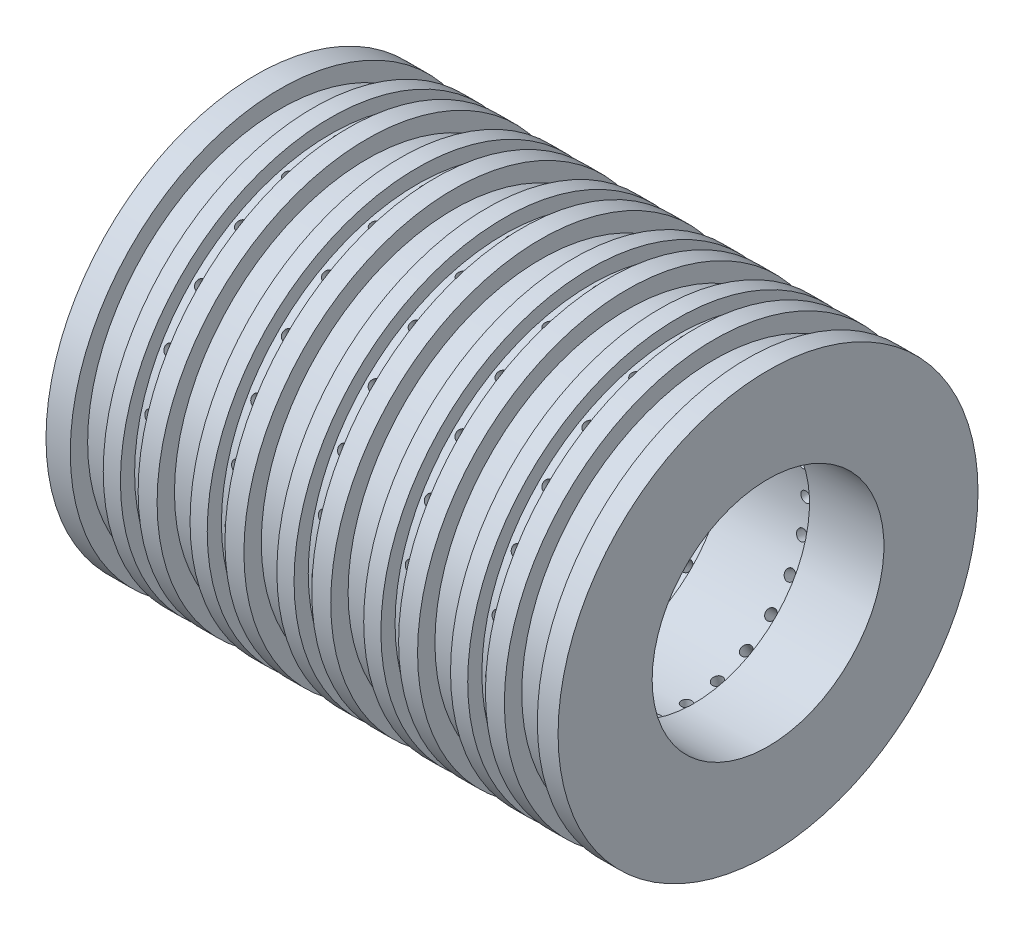
SolidWorks part; units mm, degrees
note: '?' marks a value the reader was unsure of.
ref_plane "Front Plane" through (0, 0, 0) normal (0, 0, 1) x (1, 0, 0)
ref_plane "Top Plane" through (0, 0, 0) normal (0, 1, 0) x (1, 0, 0)
ref_plane "Right Plane" through (0, 0, 0) normal (1, 0, 0) x (0, 0, -1)
sketch "Sketch1" plane through (0, 0, 0) normal (0, 0, 1) x (1, 0, 0)
  line L0 (0, 0) -> (36.5459, 0) construction
  line L1 (-6.477, 9.5758) -> (-6.477, 15.0495)
  line L3 (30.226, 15.0495) -> (30.226, 8.3058)
  line L4 (30.226, 8.3058) -> (24.892, 8.3058)
  line L5 (24.892, 8.3058) -> (24.892, 8.5598)
  line L6 (24.892, 8.5598) -> (18.669, 8.5598)
  line L7 (18.669, 8.5598) -> (18.669, 8.8138)
  line L8 (18.669, 8.8138) -> (12.446, 8.8138)
  line L9 (12.446, 8.8138) -> (12.446, 9.0678)
  line L10 (12.446, 9.0678) -> (6.223, 9.0678)
  line L11 (6.223, 9.0678) -> (6.223, 9.3218)
  line L12 (6.223, 9.3218) -> (0, 9.3218)
  line L13 (0, 9.3218) -> (0, 9.5758)
  line L14 (0, 9.5758) -> (-6.477, 9.5758)
  line L15 (-6.477, 15.0495) -> (-3.937, 15.0495)
  line L16 (-1.143, 15.0495) -> (-1.143, 14.0335)
  line L17 (-1.143, 14.0335) -> (0.127, 14.0335)
  line L18 (0.127, 14.0335) -> (0.127, 15.0495)
  line L19 (0.127, 15.0495) -> (2.4765, 15.0495)
  line L20 (5.08, 15.0495) -> (5.08, 14.0335)
  line L21 (5.08, 14.0335) -> (6.35, 14.0335)
  line L22 (6.35, 14.0335) -> (6.35, 15.0495)
  line L23 (6.35, 15.0495) -> (8.6995, 15.0495)
  line L24 (11.303, 15.0495) -> (11.303, 14.0335)
  line L25 (11.303, 14.0335) -> (12.573, 14.0335)
  line L26 (12.573, 14.0335) -> (12.573, 15.0495)
  line L27 (12.573, 15.0495) -> (14.9225, 15.0495)
  line L28 (17.526, 15.0495) -> (17.526, 14.0335)
  line L29 (17.526, 14.0335) -> (18.796, 14.0335)
  line L30 (18.796, 14.0335) -> (18.796, 15.0495)
  line L31 (18.796, 15.0495) -> (21.1455, 15.0495)
  line L32 (23.749, 15.0495) -> (23.749, 14.0335)
  line L33 (23.749, 14.0335) -> (25.019, 14.0335)
  line L34 (25.019, 14.0335) -> (25.019, 15.0495)
  line L35 (25.019, 15.0495) -> (27.4955, 15.0495)
  line L36 (-3.683, 15.0495) -> (-1.143, 15.0495)
  line L37 (2.7305, 15.0495) -> (5.08, 15.0495)
  line L38 (8.9535, 15.0495) -> (11.303, 15.0495)
  line L39 (15.1765, 15.0495) -> (17.526, 15.0495)
  line L40 (21.3995, 15.0495) -> (23.749, 15.0495)
  line L41 (27.7495, 15.0495) -> (30.226, 15.0495)
  line L42 (-3.937, 15.0495) -> (-3.683, 15.0495) construction
  line L43 (2.4765, 15.0495) -> (2.7305, 15.0495) construction
  line L44 (8.6995, 15.0495) -> (8.9535, 15.0495) construction
  line L45 (14.9225, 15.0495) -> (15.1765, 15.0495) construction
  line L46 (21.1455, 15.0495) -> (21.3995, 15.0495) construction
  line L47 (27.4955, 15.0495) -> (27.7495, 15.0495) construction
  arc A9 (21.3995, 15.0495) -> (21.1455, 15.0495) centre (21.2725, 15.0495) ccw
  arc A10 (15.1765, 15.0495) -> (14.9225, 15.0495) centre (15.0495, 15.0495) ccw
  arc A11 (8.9535, 15.0495) -> (8.6995, 15.0495) centre (8.8265, 15.0495) ccw
  arc A12 (2.7305, 15.0495) -> (2.4765, 15.0495) centre (2.6035, 15.0495) ccw
  arc A13 (-3.683, 15.0495) -> (-3.937, 15.0495) centre (-3.81, 15.0495) ccw
  arc A14 (27.7495, 15.0495) -> (27.4955, 15.0495) centre (27.6225, 15.0495) ccw
  point P37 (-6.477, 12.3126)
  dimension "D13" = 0.254
  dimension "D2" = 0.254
  dimension "D4" = 15.0495
  dimension "D5" = 1.27
  dimension "D6" = 1.016
  dimension "D8" = 1.27
  dimension "D9" = 1.016
  dimension "D10" = 1.016
  dimension "D11" = 1.27
  dimension "D3" = 6.223
  dimension "D12" = 36.703
  dimension "D14" = 9.5758
  dimension "D7" = 0.127
  dimension "D15" = 0.127
  dimension "D16" = 0.127
  dimension "D17" = 0.127
  dimension "D18" = 0.127
  dimension "D19" = 5.334
  dimension "D20" = 6.477
revolve "Revolve1" add sketch "Sketch1" angle 360 about L0
ref_plane "Plane1" through (-0.508, 0, 0) normal (-1, 0, 0) x (0, 0, 1)
ref_plane "Plane2" through (5.715, 0, 0) normal (-1, 0, 0) x (0, 0, 1)
ref_plane "Plane3" through (11.938, 0, 0) normal (1, 0, 0) x (0, 0, -1)
ref_plane "Plane4" through (18.161, 0, 0) normal (-1, 0, 0) x (0, 0, 1)
ref_plane "Plane5" through (24.384, 0, 0) normal (1, 0, 0) x (0, 0, -1)
ref_plane "Plane6" through (0, 15.0495, 0) normal (0, 1, 0) x (1, 0, 0)
ref_axis "Axis1" through (0, 0, 0) along (-1, 0, 0)?
sketch "Sketch4" plane through (-0.508, 0, 0) normal (-1, 0, 0) x (0, 0, 1)
  point P0 (0, 0)
sketch "Sketch5" plane through (5.715, 0, 0) normal (-1, 0, 0) x (0, 0, 1)
  point P0 (0, 0)
sketch "Sketch6" plane through (11.938, 0, 0) normal (1, 0, 0) x (0, 0, -1)
  point P0 (0, 0)
sketch "Sketch7" plane through (18.161, 0, 0) normal (-1, 0, 0) x (0, 0, 1)
  point P0 (0, 0)
sketch "Sketch8" plane through (24.384, 0, 0) normal (1, 0, 0) x (0, 0, -1)
  point P0 (0, 0)
sketch "Sketch9" plane through (0, 15.0495, 0) normal (0, 1, 0) x (1, 0, 0)
  point P0 (24.384, 0)
  point P2 (18.161, 0)
  point P4 (11.938, 0)
  point P6 (5.715, 0)
  point P11 (-0.508, 0)
hole_wizard "#69 (0.0292) Diameter Hole1" positions "Sketch9" profile "Sketch10" hole size "#69" standard "ANSI Inch" end condition up to next
sketch "Sketch10" plane through (24.384, 15.0495, 0) normal (1, 0, 0) x (0, 0, 1)
  line L0 (0, 0) -> (0, 6.4897)
  line L1 (0, 6.4897) -> (0.3708, 6.4897)
  line L2 (0.3708, 6.4897) -> (0.3708, 0)
  line L5 (0.3708, 0) -> (0, 0)
  line L11 (0, -6.35) -> (0, 107.95) construction
  dimension "Thru Hole Dia." = 0.7417
  dimension "Thru Hole Depth" = 6.4897
pattern_circular "CirPattern1" count 24 every 15 about axis through (0, 0, 0) along (-1, 0, 0) of "#69 (0.0292) Diameter Hole1"
sketch "Sketch11" plane through (30.226, 0, 0) normal (1, 0, 0) x (0, 0, -1)
  circle A0 centre (0, 0) radius 13.8049
  circle A1 centre (0, 0) radius 17.8435
  dimension "D1" = 27.6098
  dimension "D2" = 35.687
extrude "Cut-Extrude1" cut sketch "Sketch11" against normal blind 2.3622 from offset 1.4859 offset against normal yes
pattern_linear "LPattern1" count 6 spacing 6.223 along (-1, 0, 0) of "Cut-Extrude1"
equation "\"kero_radius\"=0.23622in"
equation "\"lox_radius\"=0.23622in"
equation "\"Cavity_width\"=0.031in"
equation "\"tooth_width\"=0.01in"
equation "\"cavity_depth\"=0.031in"
equation "\"seal_step\"=0.01in"
equation "\"purge_length\"=0.04in"
equation "\"D2@Sketch1\"=\"seal_step\""
equation "\"insert_radius\" = 0.5925in"
equation "\"recycle_groove width\" = 0.05in"
equation "\"D5@Sketch1\"=\"recycle_groove width\""
equation "\"recycle_groove_depth\" = 0.04in"
equation "\"D6@Sketch1\"=\"recycle_groove_depth\""
equation "\"N2_purge_width\"= .05in"
equation "\"N2_purge_depth\"= .04in"
equation "\"drain_width\"= .05in"
equation "\"drain_depth\"= .04in"
equation "\"D9@Sketch1\"=\"drain_depth\""
equation "\"D8@Sketch1\"=\"drain_width\""
equation "\"D10@Sketch1\"=\"N2_purge_depth\""
equation "\"D11@Sketch1\"=\"N2_purge_width\""
equation "\"radial_clearance\"= .002in"
equation "\"D3@Sketch1\"=\"tooth_width\"*5+\"Cavity_width\"*5+\"purge_length\""
equation "\"Insert_Length\"= \"D12@Sketch1\""
equation "\"InsertLength\"= 1.445in"
equation "\"D4@Sketch1\"=\"insert_radius\""
equation "\"bumb_radius\"= 0.01"
equation "\"D13@Sketch1\"=\"bumb_radius\""
equation "\"bearing_radius\"= 0.629921"
equation "\"bearing_width\"=0.393701"
equation "\"IPS_flange_width\"= .25in"
equation "\"IPS_flange_radius\" = 2.2in"
equation "\"IPS_LOX_male_radius\"= .9in"
equation "\"IPS_Kero_male_radius\" = .9in"
equation "\"IPS_radius\"= 1.4in"
equation "\"lox_in_radius\"=.375in"
equation "\"D14@Sketch1\"=\"lox_in_radius\"+\"radial_clearance\""
equation "\"D7@Sketch1\"=(\"drain_width\"-\"purge_length\")/2"
equation "\"D15@Sketch1\"=(\"drain_width\"-\"purge_length\")/2"
equation "\"D16@Sketch1\"=(\"drain_width\"-\"purge_length\")/2"
equation "\"D17@Sketch1\"=(\"drain_width\"-\"purge_length\")/2"
equation "\"D18@Sketch1\"=(\"drain_width\"-\"purge_length\")/2"
equation "\"D2@Sketch11\"=(\"insert_radius\"+\"bumb_radius\"+.1)*2"
equation "\"D19@Cut-Extrude1\"=(\"tooth_width\"*5 + \"Cavity_width\"*5+.005)/2-.0465"
equation "\"D3@LPattern1\"=\"Cavity_width\"*5+\"tooth_width\"*5+\"purge_length\""
